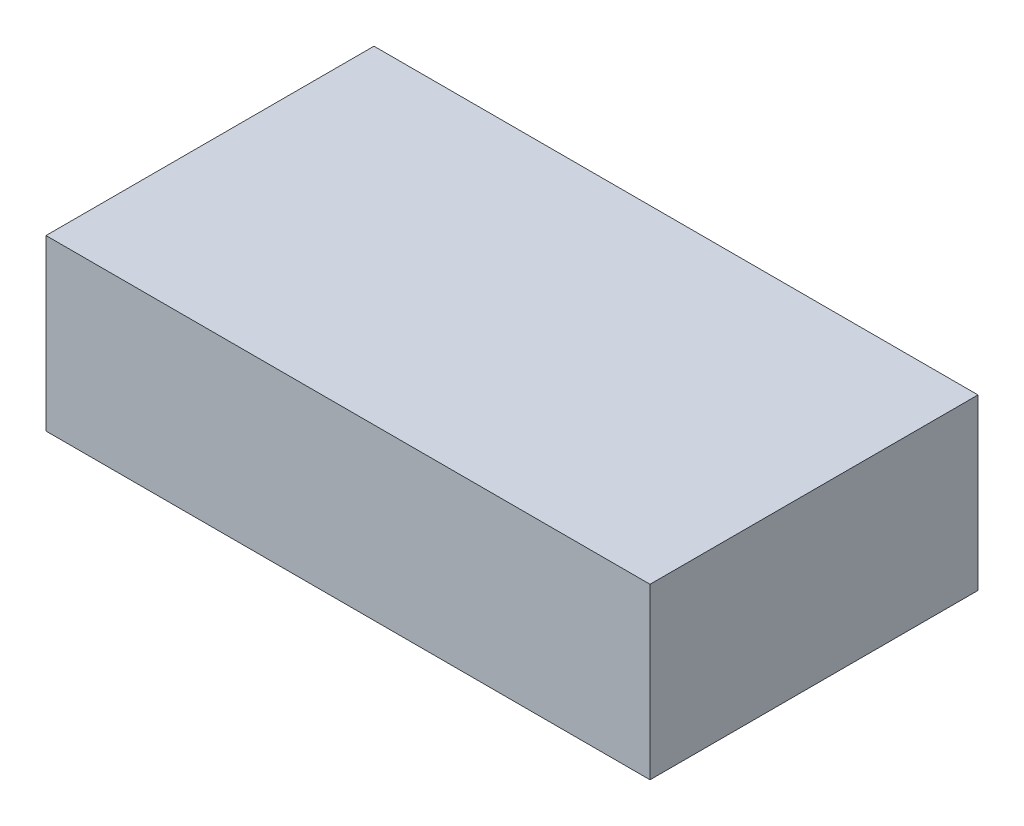
SolidWorks part; units mm, degrees
ref_plane "Plan de face" through (0, 0, 0) normal (0, 0, 1) x (1, 0, 0)
ref_plane "Plan de dessus" through (0, 0, 0) normal (0, 1, 0) x (1, 0, 0)
ref_plane "Plan de droite" through (0, 0, 0) normal (1, 0, 0) x (0, 0, -1)
sketch "Esquisse1" plane through (0, 0, 0) normal (0, 1, 0) x (1, 0, 0)
  line L0 (38.215, 0) -> (-38.215, 0)
  line L1 (38.215, 0) -> (38.215, 41.5)
  line L2 (38.215, 41.5) -> (-38.215, 41.5)
  line L3 (-38.215, 41.5) -> (-38.215, 0)
extrude "Boss.-Extru.1" add sketch "Esquisse1" along normal blind 21.43 contours L0 L3 L2 L1
